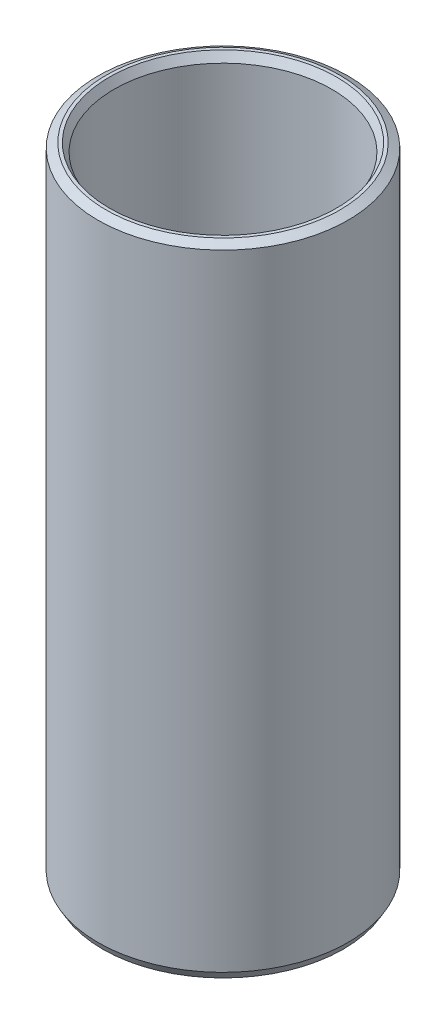
SolidWorks part; units mm, degrees
ref_plane "Front Plane" through (0, 0, 0) normal (0, 0, 1) x (1, 0, 0)
ref_plane "Top Plane" through (0, 0, 0) normal (0, 1, 0) x (1, 0, 0)
ref_plane "Right Plane" through (0, 0, 0) normal (1, 0, 0) x (0, 0, -1)
sketch "Sketch1" plane through (0, 0, 0) normal (0, 1, 0) x (1, 0, 0)
  circle A0 centre (0, 0) radius 42.5
  dimension "SLEEVE_OD" = 85
extrude "Boss-Extrude1" add sketch "Sketch1" along normal blind 217.0038
sketch "Sketch2" plane through (0, 0, 0) normal (0, 1, 0) x (1, 0, 0)
  circle A0 centre (0, 0) radius 37.0122
  dimension "BORE_D" = 74.0244
extrude "Cut-Extrude1" cut sketch "Sketch2" along normal through all
chamfer "Chamfer1" distance 1.609 angle 60 4 edges at (0, 217.0038, 37.0122) (0, 0, 37.0122) (0, 0, 42.5) (0, 217.0038, 42.5) first distance on face at (0, 217.0038, 37.0122) first distance on face at (0, 0, 37.0122) first distance on face at (0, 217.0038, 42.5)
